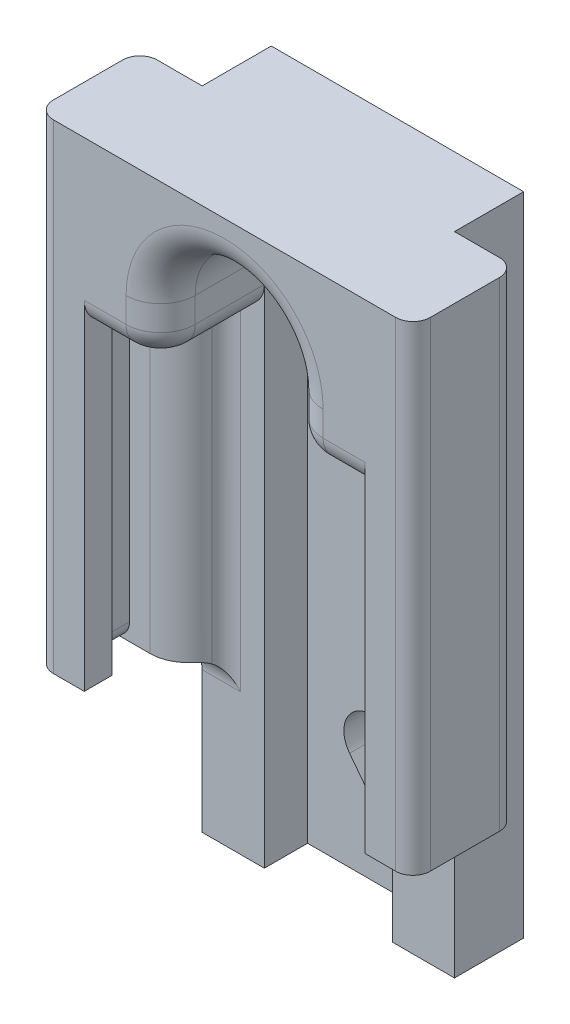
SolidWorks part; units mm, degrees
ref_plane "Front Plane" through (0, 0, 0) normal (0, 0, 1) x (1, 0, 0)
ref_plane "Top Plane" through (0, 0, 0) normal (0, 1, 0) x (1, 0, 0)
ref_plane "Right Plane" through (0, 0, 0) normal (1, 0, 0) x (0, 0, -1)
sketch "Sketch2" plane through (0, 14.7484, 0) normal (0, 1, 0) x (1, 0, 0)
  line L0 (-34.9101, -13.8993) -> (-34.9101, -15.4993) construction
  line L1 (-34.9101, -13.8993) -> (-34.9101, -15.4993) construction
  line L2 (-52.9101, -15.4993) -> (-52.9101, -13.8993) construction
  line L3 (-52.9101, -15.4993) -> (-52.9101, -13.8993) construction
  line L4 (-52.9101, -15.4993) -> (-34.9101, -15.4993) construction
  line L5 (-34.9101, -13.8993) -> (-52.9101, -13.8993) construction
  line L6 (-34.6101, -13.5993) -> (-34.6101, -15.7993)
  line L7 (-53.2101, -15.7993) -> (-34.6101, -15.7993)
  line L8 (-53.2101, -15.7993) -> (-53.2101, -13.5993)
  line L9 (-34.6101, -13.5993) -> (-53.2101, -13.5993)
  line L10 (-36.9101, -15.4993) -> (-51.5301, -15.4993) construction
  line L11 (-36.9101, -15.4993) -> (-51.5301, -15.4993)
  line L12 (-51.5301, -15.4993) -> (-51.5301, -11.3993)
  line L13 (-51.5301, -11.3993) -> (-36.9101, -11.3993)
  line L14 (-36.9101, -11.3993) -> (-36.9101, -15.4993)
  line L15 (-51.5301, -15.4993) -> (-52.0301, -15.4993)
  line L16 (-52.0301, -15.4993) -> (-52.0301, -17.3993)
  line L17 (-54.8101, -17.3993) -> (-33.0101, -17.3993)
  line L18 (-36.4101, -17.3993) -> (-36.4101, -15.4993)
  line L19 (-36.4101, -15.4993) -> (-36.9101, -15.4993)
  line L20 (-33.0101, -11.9993) -> (-33.0101, -17.3993)
  line L21 (-33.0101, -11.9993) -> (-54.8101, -11.9993)
  line L22 (-54.8101, -17.3993) -> (-54.8101, -11.9993)
  line L23 (-53.1301, -15.4993) -> (-53.1301, -9.7993)
  line L24 (-53.1301, -9.7993) -> (-35.3101, -9.7993)
  line L25 (-35.3101, -9.7993) -> (-35.3101, -15.4993)
  line L26 (-36.4101, -15.4993) -> (-36.4101, -13.5993)
  line L27 (-36.4101, -13.5993) -> (-36.4101, -11.3993)
  line L28 (-36.4101, -11.3993) -> (-36.9101, -11.3993)
  line L29 (-52.0301, -15.4993) -> (-52.0301, -13.5993)
  line L30 (-52.0301, -13.5993) -> (-52.0301, -11.3993)
  line L31 (-52.0301, -11.3993) -> (-51.5301, -11.3993)
  line L32 (-43.9101, -15.4993) -> (-43.9101, -21.2158) construction
  line L33 (-43.9101, -13.8993) -> (-43.9101, -5.0791) construction
  line L34 (-43.9101, -5.0791) -> (-51.2101, -5.0791) construction
  line L35 (-51.2101, -5.0791) -> (-51.2101, -27.4329) construction
  line L36 (-43.9101, -5.0791) -> (-36.6101, -5.0791) construction
  line L37 (-36.6101, -5.0791) -> (-36.6101, -27.4329) construction
  line L38 (-36.6101, -27.4329) -> (-51.2101, -27.4329) construction
  line L39 (-51.2101, -7.3993) -> (-36.6101, -7.3993)
  dimension "D2" = 2.5
  dimension "D3" = 0.5
  dimension "D4" = 1.6
  dimension "D6" = 14.6
  dimension "D7" = 4
  dimension "D1" = 0.3
  dimension "D5" = 1.6
sketch "Sketch3" plane through (0, 14.7484, 0) normal (0, 1, 0) x (1, 0, 0)
  line L0 (-53.2101, -15.7993) -> (-52.0301, -15.7993)
  line L1 (-52.0301, -15.7993) -> (-52.0301, -17.3993)
  line L2 (-52.0301, -17.3993) -> (-54.8101, -17.3993)
  line L3 (-54.8101, -17.3993) -> (-54.8101, -11.3993)
  line L4 (-35.3101, -9.7993) -> (-36.6101, -7.3993)
  line L5 (-51.2101, -7.3993) -> (-51.2101, -11.3993)
  line L6 (-51.2101, -11.3993) -> (-54.8101, -11.3993)
  line L7 (-35.3101, -9.7993) -> (-35.3101, -11.9993)
  line L8 (-35.3101, -11.9993) -> (-33.0101, -11.9993)
  line L9 (-33.0101, -11.9993) -> (-33.0101, -17.3993)
  line L10 (-33.0101, -17.3993) -> (-36.4101, -17.3993)
  line L11 (-36.4101, -17.3993) -> (-36.4101, -15.7993)
  line L12 (-36.4101, -15.7993) -> (-34.6101, -15.7993)
  line L13 (-34.6101, -13.5993) -> (-34.6101, -15.7993) construction
  line L14 (-34.6101, -13.5993) -> (-34.6101, -15.7993)
  line L15 (-34.6101, -13.5993) -> (-53.2101, -13.5993) construction
  line L16 (-34.6101, -13.5993) -> (-36.4101, -13.5993)
  line L17 (-53.2101, -15.7993) -> (-53.2101, -13.5993) construction
  line L18 (-53.2101, -15.7993) -> (-53.2101, -13.5993)
  line L19 (-51.5301, -11.3993) -> (-36.9101, -11.3993) construction
  line L20 (-49.8301, -11.3993) -> (-36.9101, -11.3993)
  line L21 (-36.9101, -11.3993) -> (-36.4101, -11.3993)
  line L22 (-36.4101, -11.3993) -> (-36.4101, -13.5993)
  line L26 (-52.0301, -13.5993) -> (-53.2101, -13.5993)
  line L27 (-51.2101, -7.3993) -> (-36.6101, -7.3993)
  arc A0 (-52.0301, -13.5993) -> (-49.8301, -11.3993) centre (-52.0301, -11.3993) ccw
extrude "Boss-Extrude1" add sketch "Sketch3" against normal up to vertex (18.1 mm away)
ref_plane "Plane2" through (-43.9101, 0, 0) normal (1, 0, 0) x (0, 0, -1)
split "Split1" trim tools "Plane2" bodies to split 101 resulting bodies 115
mirror "Mirror1" about plane through (-43.9101, 0, 0) normal (1, 0, 0) of bodies 115 113
sketch "Sketch5" plane through (0, 0, 0) normal (0, 0, 1) x (1, 0, 0)
  line L0 (-43.9101, 17.6984) -> (-43.9101, -6.3016) construction
  line L1 (-43.9101, 17.6984) -> (-43.9101, 25.6984) construction
  line L4 (-43.9101, 5.6984) -> (-35.0001, 5.6984) construction
  line L9 (-36.6101, 14.7484) -> (-51.2101, 14.7484)
  line L10 (-36.6101, -3.3516) -> (-36.6101, 14.7484)
  line L11 (-51.2101, 14.7484) -> (-51.2101, -3.3516) construction
  line L12 (-36.6101, 14.7484) -> (-51.2101, 14.7484)
  line L13 (-36.6101, -3.3516) -> (-36.6101, 14.7484)
  line L14 (-51.2101, -3.3516) -> (-36.6101, -3.3516) construction
  line L15 (-51.2101, -3.3516) -> (-36.6101, -3.3516)
  line L16 (-51.2101, 14.7484) -> (-51.2101, -3.3516)
  line L17 (-36.6101, 14.7484) -> (-51.2101, 14.7484)
  line L18 (-36.6101, -3.3516) -> (-36.6101, 14.7484)
  line L19 (-51.2101, -3.3516) -> (-36.6101, -3.3516)
  line L20 (-51.2101, 14.7484) -> (-51.2101, -3.3516)
  circle A0 centre (-43.9101, -6.3016) radius 1.6
  circle A1 centre (-43.9101, 17.6984) radius 1.6
  circle A2 centre (-43.9101, -6.3016) radius 3.7
  circle A3 centre (-43.9101, 17.6984) radius 3.7
  circle A4 centre (-43.9101, -6.3016) radius 6.7
  circle A5 centre (-43.9101, 17.6984) radius 6.7
  point P7 (-43.9101, -3.3516)
  dimension "D3" = 3.2
  dimension "D5" = 7.4
  dimension "D6" = 3
  dimension "D1" = 24
  dimension "D2" = 8
  dimension "D4" = 0
ref_point "Point1"
ref_plane "Plane1" through (0, 24.3984, 0) normal (0, 1, 0) x (-1, 0, 0)
sketch "Sketch4" plane through (0, 14.7484, 0) normal (0, 1, 0) x (1, 0, 0)
  line L0 (-52.0301, -15.4993) -> (-52.0301, -17.3993) construction
  line L1 (-52.0301, -15.4993) -> (-52.0301, -17.3993) construction
  line L3 (-35.7901, -17.3993) -> (-52.0301, -17.3993)
  line L16 (-53.2101, -15.7993) -> (-53.2101, -13.5993)
  line L17 (-49.8301, -11.3993) -> (-37.9901, -11.3993)
  line L18 (-49.8301, -11.3993) -> (-37.9901, -11.3993) construction
  line L19 (-35.7901, -13.5993) -> (-34.6101, -13.5993)
  line L20 (-35.7901, -13.5993) -> (-34.6101, -13.5993) construction
  line L21 (-34.6101, -13.5993) -> (-34.6101, -15.7993)
  line L22 (-34.6101, -13.5993) -> (-34.6101, -15.7993) construction
  line L23 (-34.6101, -15.7993) -> (-35.7901, -15.7993)
  line L24 (-34.6101, -15.7993) -> (-35.7901, -15.7993) construction
  line L25 (-33.0101, -11.3993) -> (-36.6101, -11.3993)
  line L26 (-33.0101, -11.3993) -> (-36.6101, -11.3993)
  line L27 (-36.6101, -11.3993) -> (-36.6101, -7.3993)
  line L28 (-54.8101, -11.3993) -> (-54.8101, -17.3993)
  line L29 (-54.8101, -17.3993) -> (-52.0301, -17.3993)
  line L30 (-52.0301, -17.3993) -> (-52.0301, -15.7993)
  line L31 (-52.0301, -15.7993) -> (-53.2101, -15.7993)
  line L37 (-35.7901, -15.7993) -> (-35.7901, -17.3993)
  line L38 (-35.7901, -15.7993) -> (-35.7901, -17.3993) construction
  line L39 (-35.7901, -17.3993) -> (-33.0101, -17.3993)
  line L40 (-35.7901, -17.3993) -> (-33.0101, -17.3993)
  line L41 (-36.6101, -11.3993) -> (-36.6101, -7.3993)
  line L42 (-36.6101, -7.3993) -> (-51.2101, -7.3993)
  line L43 (-36.6101, -7.3993) -> (-51.2101, -7.3993)
  line L44 (-54.8101, -11.3993) -> (-54.8101, -17.3993)
  line L45 (-54.8101, -17.3993) -> (-52.0301, -17.3993)
  line L47 (-51.2101, -7.3993) -> (-51.2101, -11.3993)
  line L48 (-51.2101, -7.3993) -> (-51.2101, -11.3993)
  line L49 (-51.2101, -11.3993) -> (-54.8101, -11.3993)
  line L50 (-53.2101, -13.5993) -> (-52.0301, -13.5993)
  line L51 (-33.0101, -17.3993) -> (-33.0101, -11.3993)
  line L52 (-51.2101, -11.3993) -> (-54.8101, -11.3993)
  line L53 (-33.0101, -17.3993) -> (-33.0101, -11.3993)
  arc A2 (-37.9901, -11.3993) -> (-35.7901, -13.5993) centre (-35.7901, -11.3993) ccw
  arc A3 (-37.9901, -11.3993) -> (-35.7901, -13.5993) centre (-35.7901, -11.3993) ccw construction
  arc A4 (-52.0301, -13.5993) -> (-49.8301, -11.3993) centre (-52.0301, -11.3993) ccw
  arc A5 (-52.0301, -13.5993) -> (-49.8301, -11.3993) centre (-52.0301, -11.3993) ccw construction
  dimension "D1" = 0
extrude "Boss-Extrude2" add sketch "Sketch4" along direction (0, 1, 0) on the side of the normal up to surface (9.65 mm away) up to plane "Plane1"
sketch "Sketch13" plane through (0, 0, 7.3993) normal (0, 0, -1) x (-1, 0, 0)
  line L0 (36.6101, -6.3016) -> (36.6101, -3.3516)
  line L1 (36.6101, -3.3516) -> (51.2101, -3.3516) construction
  line L2 (36.6101, -3.3516) -> (51.2101, -3.3516)
  line L3 (51.2101, -3.3516) -> (51.2101, -6.3016)
  line L4 (36.6101, -6.3016) -> (36.6101, -13.0016)
  line L5 (36.6101, -13.0016) -> (51.2101, -13.0016)
  line L6 (51.2101, -13.0016) -> (51.2101, -6.3016)
  line L8 (36.6101, -3.3516) -> (36.6101, 24.3984) construction
  circle A0 centre (43.9101, -6.3016) radius 6.7 construction
  dimension "D1" = 9.65
extrude "Boss-Extrude3" add sketch "Sketch13" against normal up to vertex
sketch "Sketch14" plane through (0, 0, 17.3993) normal (0, 0, 1) x (1, 0, 0)
  circle A0 centre (-43.9101, -6.3016) radius 3.7 construction
  circle A1 centre (-43.9101, 17.6984) radius 3.7 construction
  circle A2 centre (-43.9101, -6.3016) radius 3.7
  circle A3 centre (-43.9101, 17.6984) radius 3.7
sketch "Sketch9" plane through (0, 0, 17.3993) normal (0, 0, 1) x (1, 0, 0)
  line L2 (-40.2101, 17.6984) -> (-40.2101, -6.3016)
  line L4 (-47.6101, 17.6984) -> (-47.6101, -6.3016)
  circle A0 centre (-43.9101, 17.6984) radius 3.7 construction
  arc A1 (-40.2101, 17.6984) -> (-47.6101, 17.6984) centre (-43.9101, 17.6984) ccw
  circle A2 centre (-43.9101, -6.3016) radius 3.7 construction
  arc A3 (-47.6101, -6.3016) -> (-40.2101, -6.3016) centre (-43.9101, -6.3016) ccw
sketch "Sketch12" plane through (0, 0, 17.3993) normal (0, 0, 1) x (1, 0, 0)
  line L0 (-43.9101, 17.6984) -> (-43.9101, -6.3016) construction
  line L1 (-43.9101, -6.3016) -> (-43.9101, -14.7177) construction
  line L2 (-43.9101, 12.3091) -> (-41.366, 15.0034) construction
  line L3 (-41.366, 15.0034) -> (-46.4542, 15.0034) construction
  line L4 (-46.4542, 15.0034) -> (-43.9101, 12.3091) construction
  line L7 (-40.2101, -6.3016) -> (-40.2101, -14.7177)
  line L8 (-40.2101, -14.7177) -> (-47.6101, -14.7177)
  line L9 (-47.6101, -6.3016) -> (-47.6101, -14.7177)
  line L11 (-47.6101, 17.6984) -> (-47.6101, -6.3016)
  line L13 (-40.2101, -6.3016) -> (-40.2101, 17.6984)
  arc A2 (-40.2101, 17.6984) -> (-47.6101, 17.6984) centre (-43.9101, 17.6984) ccw
  arc A7 (-47.6101, -6.3016) -> (-40.2101, -6.3016) centre (-43.9101, -6.3016) ccw construction
extrude "Cut-Extrude4" cut sketch "Sketch12" against normal offset from surface (8.5 mm away) 1.5 up to face at (-43.9101, 5.6984, 7.3993)
sketch "Sketch15" plane through (0, 0, 8.8993) normal (0, 0, 1) x (1, 0, 0)
  line L0 (-43.9101, 17.6984) -> (-43.9101, -10.3867) construction
  line L1 (-42.6407, -7.2756) -> (-43.9101, -8.9299)
  line L2 (-43.9101, -8.9299) -> (-45.1794, -7.2756)
  line L4 (-45.1794, 16.7244) -> (-43.9101, 15.0701)
  line L5 (-43.9101, 15.0701) -> (-42.6407, 16.7244)
  circle A0 centre (-43.9101, -6.3016) radius 1.6 construction
  circle A1 centre (-43.9101, 17.6984) radius 1.6 construction
  arc A2 (-42.6407, -7.2756) -> (-45.1794, -7.2756) centre (-43.9101, -6.3016) ccw
  arc A3 (-42.6407, 16.7244) -> (-45.1794, 16.7244) centre (-43.9101, 17.6984) ccw
  dimension "D2" = 75
  dimension "D1" = 75
extrude "Cut-Extrude6" cut sketch "Sketch15" against normal through all
fillet "Fillet1" radius 1 6 edges at (-34.6101, -3.3516, 14.6993) (-53.2101, -3.3516, 14.6993) (-33.0101, 10.5234, 11.3993) (-33.0101, 10.5234, 17.3993) (-54.8101, 10.5234, 17.3993) (-54.8101, 10.5234, 11.3993)
fillet "Fillet2" radius 1 2 edges
fillet "Fillet3" radius 2 3 edges at (-40.2101, 16.2234, 17.3993) (-47.6101, 16.2234, 17.3993) (-43.9101, 21.3984, 17.3993)
fillet "Fillet4" radius 1.5 6 edges at (-47.6101, 14.7484, 13.3993) (-48.1959, 14.7484, 16.8136) (-40.2101, 14.7484, 13.3993) (-39.6243, 14.7484, 16.8136)
fillet "Fillet5" radius 1.5 2 edges
